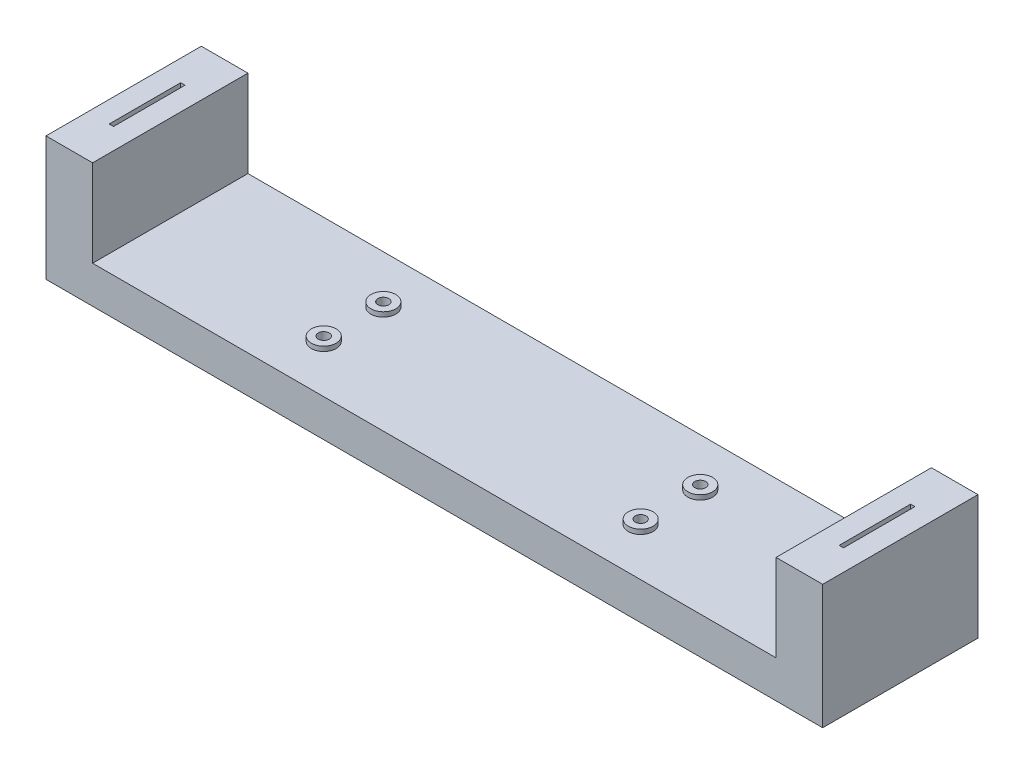
SolidWorks part; units mm, degrees
ref_plane "Front Plane" through (0, 0, 0) normal (0, 0, 1) x (1, 0, 0)
ref_plane "Top Plane" through (0, 0, 0) normal (0, 1, 0) x (1, 0, 0)
ref_plane "Right Plane" through (0, 0, 0) normal (1, 0, 0) x (0, 0, -1)
sketch "Sketch1" plane through (0, 0, 0) normal (0, 1, 0) x (1, 0, 0)
  line L0 (-125, 25) -> (-110, 25)
  line L1 (125, -25) -> (-125, -25)
  line L2 (125, -25) -> (125, 25)
  line L3 (125, 25) -> (-125, 25)
  line L4 (-125, -25) -> (-125, 25)
  line L5 (125, -25) -> (-125, 25) construction
  line L6 (125, 25) -> (-125, -25) construction
  line L7 (-110, 25) -> (-110, -25)
  line L8 (-110, -25) -> (-125, -25)
  line L10 (110, 0) -> (110, 25)
  line L11 (110, 25) -> (125, 25)
  line L12 (110, 0) -> (110, -25)
  circle A0 centre (51.0068, 9.5904) radius 1.75
  circle A1 centre (51.0068, -9.5904) radius 1.75
  circle A2 centre (-51.0068, -9.5904) radius 1.75
  point P0 (0, 0)
extrude "Boss-Extrude1" add sketch "Sketch1" along normal blind 40 contours L7 L0 L4 L1 region at (-117.5, 0, 0)
extrude "Boss-Extrude2" add sketch "Sketch1<4>" along normal blind 40 separate body contours L10 L12 L1 L2 L3 region at (117.5, 0, 0)
sketch "Sketch1<4>" plane through (0, 0, 0) normal (0, 1, 0) x (1, 0, 0) same geometry as "Sketch1"
extrude "Boss-Extrude3" add sketch "Sketch1<6>" along normal blind 12 contours L12 L10 L3 L7 L1 region at (-0.0447, 0, -0.0084)
sketch "Sketch1<6>" plane through (0, 0, 0) normal (0, 1, 0) x (1, 0, 0) same geometry as "Sketch1"
sketch "Sketch2" plane through (0, 40, 0) normal (0, 1, 0) x (1, 0, 0)
  line L4 (-116.75, -11.5) -> (-118.15, -11.5)
  line L5 (-116.75, -11.5) -> (-116.75, 11.5)
  line L6 (-116.75, 11.5) -> (-118.15, 11.5)
  line L7 (-118.15, -11.5) -> (-118.15, 11.5)
  line L8 (-116.75, -11.5) -> (-118.15, 11.5) construction
  line L9 (-116.75, 11.5) -> (-118.15, -11.5) construction
  point P6 (-117.45, 0)
extrude "Cut-Extrude1" cut sketch "Sketch2" against normal blind 30
sketch "Sketch3" plane through (0, 40, 0) normal (0, 1, 0) x (1, 0, 0)
  line L4 (116.8, -11.5) -> (118.2, -11.5)
  line L5 (116.8, -11.5) -> (116.8, 11.5)
  line L6 (116.8, 11.5) -> (118.2, 11.5)
  line L7 (118.2, -11.5) -> (118.2, 11.5)
  line L8 (116.8, -11.5) -> (118.2, 11.5) construction
  line L9 (116.8, 11.5) -> (118.2, -11.5) construction
  point P6 (117.5, 0)
extrude "Cut-Extrude2" cut sketch "Sketch3" against normal blind 30
sketch "Sketch4" plane through (0, 12, 0) normal (0, 1, 0) x (1, 0, 0)
  circle A0 centre (-51.0068, 9.5904) radius 1.75
extrude "Cut-Extrude5" cut sketch "Sketch4" against normal blind 25
sketch "Sketch5" plane through (0, 12, 0) normal (0, 1, 0) x (1, 0, 0)
  circle A0 centre (-51.0068, -9.5904) radius 1.75
  circle A1 centre (-51.0068, -9.5904) radius 4
extrude "Boss-Extrude4" add sketch "Sketch5" along normal blind 1.5
sketch "Sketch6" plane through (0, 12, 0) normal (0, 1, 0) x (1, 0, 0)
  circle A0 centre (-51.0068, 9.5904) radius 1.75
  circle A1 centre (-51.0068, 9.5904) radius 4
  circle A2 centre (51.0068, 9.5904) radius 1.75
  circle A3 centre (51.0068, 9.5904) radius 4
  circle A4 centre (51.0068, -9.5904) radius 4
  circle A5 centre (51.0068, -9.5904) radius 1.75
extrude "Boss-Extrude5" add sketch "Sketch6" along normal blind 1.5
